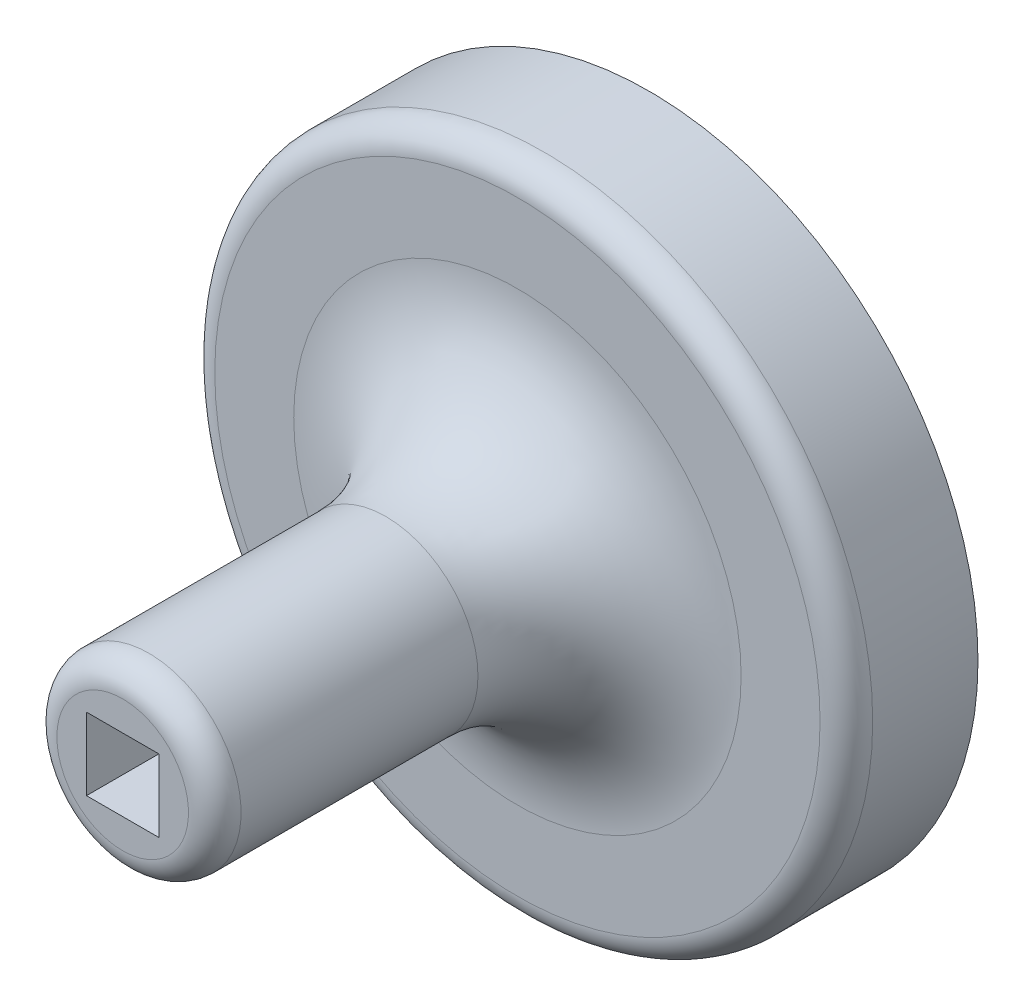
SolidWorks part; units mm, degrees
ref_plane "Plan de face" through (0, 0, 0) normal (0, 0, 1) x (1, 0, 0)
ref_plane "Plan de dessus" through (0, 0, 0) normal (0, 1, 0) x (1, 0, 0)
ref_plane "Plan de droite" through (0, 0, 0) normal (1, 0, 0) x (0, 0, -1)
sketch "Esquisse1" plane through (0, 0, 0) normal (0, 0, 1) x (1, 0, 0)
  circle A0 centre (0, 0) radius 25
  dimension "D1" = 50
extrude "Boss.-Extru.1" add sketch "Esquisse1" along normal blind 10
sketch "Esquisse2" plane through (0, 0, 0) normal (0, 0, -1) x (-1, 0, 0)
  circle A0 centre (0, 0) radius 7
  dimension "D1" = 14
extrude "Boss.-Extru.2" add sketch "Esquisse2" against normal blind 40
sketch "Esquisse3" plane through (0, 0, 0) normal (0, 0, -1) x (-1, 0, 0)
  line L1 (-2.75, 2.75) -> (2.75, 2.75)
  line L2 (-2.75, 2.75) -> (-2.75, -2.75)
  line L3 (-2.75, -2.75) -> (2.75, -2.75)
  line L4 (2.75, 2.75) -> (2.75, -2.75)
  line L5 (-2.75, 2.75) -> (2.75, -2.75) construction
  line L6 (-2.75, -2.75) -> (2.75, 2.75) construction
  point P0 (0, 0)
  dimension "D1" = 5.5
extrude "Enlèv. mat.-Extru.1" cut sketch "Esquisse3" against normal blind 40
fillet "Congé1" radius 10 1 edges at (7, 0, 10)
fillet "Congé2" radius 2 2 edges at (25, 0, 10) (-7, 0, 40)
